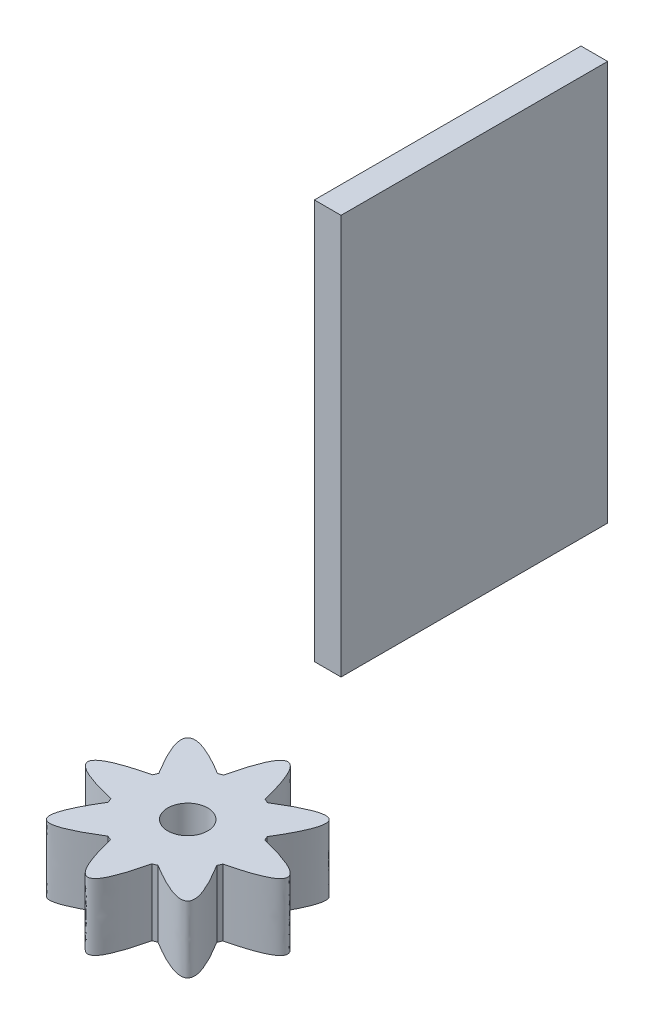
SolidWorks part; units mm, degrees
ref_plane "Front Plane" through (0, 0, 0) normal (0, 0, 1) x (1, 0, 0)
ref_plane "Top Plane" through (0, 0, 0) normal (0, 1, 0) x (1, 0, 0)
ref_plane "Right Plane" through (0, 0, 0) normal (1, 0, 0) x (0, 0, -1)
sketch "Sketch1" plane through (0, 0, 0) normal (0, 1, 0) x (1, 0, 0)
  line L1 (-25, 25) -> (25, 25)
  line L2 (-25, 25) -> (-25, -25)
  line L3 (-25, -25) -> (25, -25)
  line L4 (25, 25) -> (25, -25)
  line L5 (-25, 25) -> (25, -25) construction
  line L6 (-25, -25) -> (25, 25) construction
  point P0 (0, 0)
  dimension "D1" = 50
  dimension "D2" = 50
sketch "Sketch2" plane through (0, 0, 0) normal (0, 1, 0) x (1, 0, 0)
  line L1 (-29, 10) -> (-27, 10)
  line L2 (-29, 10) -> (-29, -10)
  line L3 (-29, -10) -> (-27, -10)
  line L4 (-27, 10) -> (-27, -10)
  point P4 (-27, 0)
  dimension "D1" = 2
  dimension "D2" = 20
  dimension "D3" = 27
  dimension "D4" = 10
sketch "Sketch3" plane through (0, 0, 0) normal (0, 1, 0) x (1, 0, 0)
  line L1 (-6.002, -35) -> (-6, -38) construction
  circle A1 centre (-6, -42.5) radius 4.5
  dimension "D1" = 9
  dimension "D2" = 42.5
  dimension "D3" = 6
extrude "Boss-Extrude2" add sketch "Sketch3" along normal mid plane 5 contours A1
sketch "Sketch5" plane through (0, -2.5, 0) normal (0, -1, 0) x (1, 0, 0)
  line L0 (-7.5809, 46.7132) -> (-4.4606, 46.7285)
  circle A0 centre (-6, 42.5) radius 4.5 construction
  spline S0 degree 2 poles (-7.5809, 46.7132) (-5.9929, 53.2792) (-4.4606, 46.7285) knots 0 0 0 1 1 1
  dimension "D1" = 7.5
  dimension "D2" = 3.1204
extrude "Boss-Extrude3" add sketch "Sketch5" against normal through all
pattern_circular "CirPattern1" count 8 over 360 about axis through (-6, -2.5, 42.5) along (0, 1, 0) of "Boss-Extrude3"
sketch "Sketch7" plane through (0, -2.5, 0) normal (0, -1, 0) x (1, 0, 0)
  circle A0 centre (-6, 42.5) radius 1.5
extrude "Cut-Extrude1" cut sketch "Sketch7" against normal blind 5
extrude "Boss-Extrude4" add sketch "Sketch2" along normal mid plane 30 separate body contours L2 L3 L4 L1
sketch "Sketch8" plane through (0, 0, 0) normal (0, 1, 0) x (1, 0, 0)
  line L0 (-29, 10) -> (-29, -10) construction
  parabola Q0 (-10.0785, -40.5986) -> (-7.8613, -38.403) focus (-11.1691, -37.3249) apex (-11.3009, -37.1943) construction
  parabola Q1 (-7.9014, -46.5785) -> (-10.097, -44.3613) focus (-11.1751, -47.6691) apex (-11.3057, -47.8009) construction
  spline S0 degree 2 poles (-29, -5.1107) (-46.7471, -31.9729) (-11.3009, -37.1943) knots 0 0 0 1 1 1
  spline S1 degree 3 poles (-29, 5.9761) (-53.9636, -5.6433) (-56.85, -53.2483) (-8.4371, -46.9026) knots 0 0 0 0 1 1 1 1
  point P2 (-46.5712, -20.4531)
